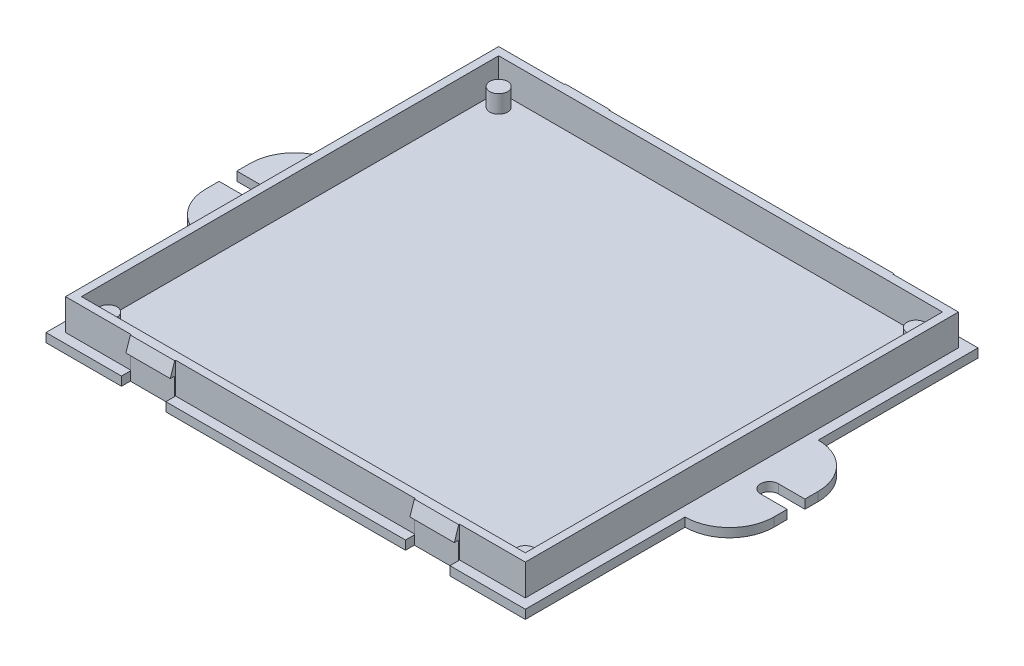
SolidWorks part; units mm, degrees
ref_plane "Front Plane" through (0, 0, 0) normal (0, 0, 1) x (1, 0, 0)
ref_plane "Top Plane" through (0, 0, 0) normal (0, 1, 0) x (1, 0, 0)
ref_plane "Right Plane" through (0, 0, 0) normal (1, 0, 0) x (0, 0, -1)
sketch "Sketch1" plane through (0, 0, 0) normal (0, 1, 0) x (1, 0, 0)
  line L1 (-54, 51) -> (54, 51)
  line L2 (-54, 51) -> (-54, -51)
  line L3 (-54, -51) -> (54, -51)
  line L4 (54, 51) -> (54, -51)
  line L5 (-54, 51) -> (54, -51) construction
  line L6 (-54, -51) -> (54, 51) construction
  point P0 (0, 0)
  dimension "D1" = 102
  dimension "D2" = 108
extrude "Boss-Extrude1" add sketch "Sketch1" along normal blind 2
sketch "Sketch2" plane through (0, 2, 0) normal (0, 1, 0) x (1, 0, 0)
  line L1 (-52, 49) -> (52, 49)
  line L2 (-52, 49) -> (-52, -49)
  line L3 (-52, -49) -> (52, -49)
  line L4 (52, 49) -> (52, -49)
  line L5 (-52, 49) -> (52, -49) construction
  line L6 (-52, -49) -> (52, 49) construction
  point P0 (0, 0)
  dimension "D1" = 98
  dimension "D2" = 104
extrude "Boss-Extrude2" add sketch "Sketch2" along normal blind 7
sketch "Sketch3" plane through (0, 9, 0) normal (0, 1, 0) x (1, 0, 0)
  line L8 (50, -47) -> (50, 47)
  line L9 (50, 47) -> (-50, 47)
  line L10 (-50, 47) -> (-50, -47)
  line L11 (-50, -47) -> (50, -47)
  line L12 (50, -47) -> (50, 47)
  line L13 (50, 47) -> (-50, 47)
  line L14 (-50, 47) -> (-50, -47)
  line L15 (-50, -47) -> (50, -47)
  dimension "D1" = 2
extrude "Cut-Extrude1" cut sketch "Sketch3" against normal blind 7
sketch "Sketch4" plane through (0, 0, 49) normal (0, 0, 1) x (1, 0, 0)
  line L0 (-52, 9) -> (-37, 9)
  line L1 (-52, 9) -> (52, 9) construction
  line L2 (52, 9) -> (32.2553, 9)
  line L4 (-37, 9) -> (-27, 9)
  line L5 (-37, 9) -> (-37, 6)
  line L6 (-37, 6) -> (-27, 6)
  line L7 (-27, 9) -> (-27, 6)
  dimension "D1" = 15
  dimension "D2" = 10
  dimension "D3" = 3
extrude "Boss-Extrude6" add sketch "Sketch4" along normal blind 1 contours L5 L4 L7 L6
sketch "Sketch5" plane through (-27, 0, 0) normal (1, 0, 0) x (0, 0, -1)
  line L0 (-50, 6) -> (-49, 9)
  line L1 (-49, 9) -> (-50, 9)
  line L2 (-50, 9) -> (-50, 5.9638)
  line M2 (-49, 9) -> (-50, 9)
  line M3 (-50, 9) -> (-50, 6)
extrude "Cut-Extrude2" cut sketch "Sketch5" against normal blind 10 contours L0 M3 M2 region at (-27, 8, 49.6667)
sketch "Sketch6" plane through (0, 0, 49) normal (0, 0, 1) x (1, 0, 0)
  line L0 (52, 9) -> (37, 9)
  line L1 (-27, 9) -> (52, 9) construction
  line L3 (37, 9) -> (27, 9)
  line L4 (37, 9) -> (37, 6)
  line L5 (37, 6) -> (27, 6)
  line L6 (27, 9) -> (27, 6)
  dimension "D1" = 15
  dimension "D2" = 10
  dimension "D3" = 3
extrude "Boss-Extrude7" add sketch "Sketch6" along normal blind 1 contours L4 L3 L6 L5
sketch "Sketch7" plane through (37, 0, 0) normal (1, 0, 0) x (0, 0, -1)
  line L0 (-50, 6) -> (-49, 9)
  line L1 (-49, 9) -> (-50, 9)
  line L2 (-50, 9) -> (-50, 6)
extrude "Cut-Extrude3" cut sketch "Sketch7" against normal blind 10
sketch "Sketch9" plane through (0, 0, -49) normal (0, 0, -1) x (-1, 0, 0)
  line L0 (-52, 9) -> (-37, 9)
  line L1 (-52, 9) -> (52, 9) construction
  line L3 (-37, 9) -> (-27, 9)
  line L4 (-37, 9) -> (-37, 6)
  line L5 (-37, 6) -> (-27, 6)
  line L6 (-27, 9) -> (-27, 6)
  dimension "D1" = 15
  dimension "D2" = 10
  dimension "D3" = 3
extrude "Boss-Extrude9" add sketch "Sketch9" along normal blind 1 contours L4 L3 L6 L5
sketch "Sketch10" plane through (27, 0, 0) normal (-1, 0, 0) x (0, 0, 1)
  line L0 (-49, 9) -> (-50, 6)
  line L1 (-50, 6) -> (-50, 9)
  line L2 (-50, 9) -> (-49, 9)
extrude "Cut-Extrude4" cut sketch "Sketch10" against normal blind 10
sketch "Sketch11" plane through (0, 0, -49) normal (0, 0, -1) x (-1, 0, 0)
  line L0 (52, 9) -> (37, 9)
  line L1 (-27, 9) -> (52, 9) construction
  line L3 (37, 9) -> (27, 9)
  line L4 (37, 9) -> (37, 6)
  line L5 (37, 6) -> (27, 6)
  line L6 (27, 9) -> (27, 6)
  dimension "D1" = 15
  dimension "D2" = 10
  dimension "D3" = 3
extrude "Boss-Extrude10" add sketch "Sketch11" along normal blind 1 contours L4 L3 L6 L5
sketch "Sketch12" plane through (-37, 0, 0) normal (-1, 0, 0) x (0, 0, 1)
  line L0 (-49, 9) -> (-50, 6)
  line L1 (-50, 6) -> (-50, 9)
  line L2 (-50, 9) -> (-49, 9)
extrude "Cut-Extrude5" cut sketch "Sketch12" against normal blind 10 contours L2 L0 L1
sketch "Sketch20" plane through (0, 0, 51) normal (0, 0, 1) x (1, 0, 0)
  line L0 (54, 2) -> (37, 2)
  line L1 (-54, 2) -> (54, 2) construction
  line L2 (-54, 0) -> (54, 0) construction
  line L3 (37, 2) -> (27, 2)
  line L4 (37, 2) -> (37, 0)
  line L5 (37, 0) -> (27, 0)
  line L6 (27, 2) -> (27, 0)
  line M6 (-54, 0) -> (54, 0)
  line M8 (54, 2) -> (-54, 2)
  dimension "D1" = 17
  dimension "D2" = 10
extrude "Cut-Extrude7" cut sketch "Sketch20" against normal blind 2 contours L6 L4 M8 M6 region at (32, 1, 51)
sketch "Sketch21" plane through (0, 2, 0) normal (0, 1, 0) x (1, 0, 0)
  line L0 (-52, -49) -> (-37, -49)
  line L1 (-52, -49) -> (27, -49) construction
  line L2 (-54, -51) -> (27, -51) construction
  line L3 (-37, -49) -> (-27, -49)
  line L4 (-37, -49) -> (-37, -51)
  line L5 (-37, -51) -> (-27, -51)
  line L6 (-27, -49) -> (-27, -51)
  dimension "D1" = 15
  dimension "D2" = 10
extrude "Cut-Extrude8" cut sketch "Sketch21" against normal blind 2 contours L4 L3 L6 L5
sketch "Sketch22" plane through (0, 2, 0) normal (0, 1, 0) x (1, 0, 0)
  line L0 (52, 49) -> (37, 49)
  line L1 (52, 49) -> (-52, 49) construction
  line L2 (54, 51) -> (-54, 51) construction
  line L3 (37, 49) -> (27, 49)
  line L4 (37, 49) -> (37, 51)
  line L5 (37, 51) -> (27, 51)
  line L6 (27, 49) -> (27, 51)
  line M6 (-52, 49) -> (52, 49)
  line M12 (54, 51) -> (-54, 51)
  dimension "D1" = 15
  dimension "D2" = 10
extrude "Cut-Extrude9" cut sketch "Sketch22" against normal blind 2 contours L6 L4 M6 M12 region at (32, 2, -50)
sketch "Sketch23" plane through (0, 2, 0) normal (0, 1, 0) x (1, 0, 0)
  line L0 (-52, 49) -> (-37, 49)
  line L1 (27, 49) -> (-52, 49) construction
  line L2 (27, 51) -> (-54, 51) construction
  line L3 (-37, 49) -> (-27, 49)
  line L4 (-37, 49) -> (-37, 51)
  line L5 (-37, 51) -> (-27, 51)
  line L6 (-27, 49) -> (-27, 51)
  dimension "D1" = 15
  dimension "D2" = 10
extrude "Cut-Extrude11" cut sketch "Sketch23" against normal blind 2 contours L4 L3 L6 L5
sketch "Sketch24" plane through (0, 2, 0) normal (0, 1, 0) x (1, 0, 0)
  line L1 (50, 47) -> (47, 47)
  line L2 (50, 47) -> (50, 44)
  line L3 (50, 44) -> (47, 44)
  line L4 (47, 47) -> (47, 44)
  circle A0 centre (47, 44) radius 2
  dimension "D1" = 3
  dimension "D2" = 3
extrude "Boss-Extrude11" add sketch "Sketch24" along normal blind 4 contours A0
sketch "Sketch25" plane through (0, 2, 0) normal (0, 1, 0) x (1, 0, 0)
  line L1 (-50, 47) -> (-47, 47)
  line L2 (-50, 47) -> (-50, 44)
  line L3 (-50, 44) -> (-47, 44)
  line L4 (-47, 47) -> (-47, 44)
  circle A0 centre (-47, 44) radius 2
  dimension "D1" = 3
  dimension "D2" = 3
extrude "Boss-Extrude12" add sketch "Sketch25" along normal blind 4 contours L3 A0 L4 | L4 A0 L3 region at (-46.7171, 2, -43.7171) region at (-47.8488, 2, -44.8488)
sketch "Sketch26" plane through (0, 2, 0) normal (0, 1, 0) x (1, 0, 0)
  line L1 (-50, -47) -> (-47, -47)
  line L2 (-50, -47) -> (-50, -44)
  line L3 (-50, -44) -> (-47, -44)
  line L4 (-47, -47) -> (-47, -44)
  circle A0 centre (-47, -44) radius 2
  dimension "D1" = 3
  dimension "D2" = 3
extrude "Boss-Extrude13" add sketch "Sketch26" along normal blind 4 contours L3 A0 L4 | L4 A0 L3 region at (-47.8488, 2, 44.8488) region at (-46.7171, 2, 43.7171)
sketch "Sketch27" plane through (0, 2, 0) normal (0, 1, 0) x (1, 0, 0)
  line L1 (50, -47) -> (47, -47)
  line L2 (50, -47) -> (50, -44)
  line L3 (50, -44) -> (47, -44)
  line L4 (47, -47) -> (47, -44)
  circle A0 centre (47, -44) radius 2
  dimension "D1" = 3
  dimension "D2" = 3
extrude "Boss-Extrude14" add sketch "Sketch27" along normal blind 4 contours L4 A0 L3 | L3 A0 L4 region at (46.7171, 2, 43.7171) region at (47.8488, 2, 44.8488)
sketch "Sketch28" plane through (-54, 0, 0) normal (-1, 0, 0) x (0, 0, 1)
  line L0 (-51, 1) -> (51, 1)
  line L1 (-51, 2) -> (-51, 0) construction
  line L2 (51, 2) -> (51, 0) construction
  line L3 (-51, 0) -> (51, 0) construction
  line L4 (-15, 2) -> (15, 2)
  line L5 (-15, 2) -> (-15, 0)
  line L6 (-15, 0) -> (15, 0)
  line L7 (15, 2) -> (15, 0)
  line L8 (-15, 2) -> (15, 0) construction
  line L9 (-15, 0) -> (15, 2) construction
  point P7 (0, 1)
  dimension "D1" = 30
extrude "Boss-Extrude15" add sketch "Sketch28" along normal blind 10 contours L6 L7 L4 L5
sketch "Sketch29" plane through (0, 2, 0) normal (0, 1, 0) x (1, 0, 0)
  line L0 (-64, 2) -> (-64, -2)
  line L1 (-64, 15) -> (-64, -15) construction
  line L3 (-64, 2) -> (-58, 2)
  line L4 (-64, 2) -> (-64, -2)
  line L5 (-64, -2) -> (-58, -2)
  line L6 (-58, 2) -> (-58, -2)
  circle A0 centre (-58, 0) radius 2
  point P5 (-64, 0)
  dimension "D1" = 4
  dimension "D2" = 6
extrude "Cut-Extrude12" cut sketch "Sketch29" against normal blind 2 contours L6 A0 | L4 L3 L6 L5 region at (-57.1512, 2, 0)
fillet "Fillet1" radius 10 2 edges at (-64, 1, 15) (-64, 1, -15)
sketch "Sketch30" plane through (54, 0, 0) normal (1, 0, 0) x (0, 0, -1)
  line L0 (-51, 1) -> (51, 1)
  line L1 (-51, 2) -> (-51, 0) construction
  line L2 (51, 2) -> (51, 0) construction
  line L3 (-51, 0) -> (51, 0) construction
  line L4 (-15, 2) -> (15, 2)
  line L5 (-15, 2) -> (-15, 0)
  line L6 (-15, 0) -> (15, 0)
  line L7 (15, 2) -> (15, 0)
  line L8 (-15, 2) -> (15, 0) construction
  line L9 (-15, 0) -> (15, 2) construction
  point P6 (0, 1)
  line M2 (-51, 0) -> (51, 0)
  line M4 (51, 2) -> (-51, 2)
  dimension "D1" = 30
extrude "Boss-Extrude16" add sketch "Sketch30" along normal blind 10 contours L7 L5 L0 M4 | L7 L0 L5 M2 region at (54, 1.5, 0) region at (54, 0.5, 0)
sketch "Sketch32" plane through (0, 2, 0) normal (0, 1, 0) x (1, 0, 0)
  line L0 (64, -2) -> (64, 2)
  line L1 (64, 15) -> (64, -15) construction
  line L3 (64, -2) -> (58, -2)
  line L4 (64, -2) -> (64, 2)
  line L5 (64, 2) -> (58, 2)
  line L6 (58, -2) -> (58, 2)
  circle A0 centre (58, 0) radius 2
  point P5 (64, 0)
  line M14 (64, -15) -> (64, 15)
  dimension "D1" = 4
  dimension "D2" = 6
extrude "Cut-Extrude13" cut sketch "Sketch32" against normal blind 2 contours A0 L3 L5 M14 | L6 A0 | L6 A0 region at (61.7629, 2, 0) region at (57.1512, 2, 0) region at (58.8488, 2, 0)
fillet "Fillet2" radius 10 2 edges at (64, 1, -15) (64, 1, 15)
sketch "Sketch33" plane through (0, 9, 0) normal (0, 1, 0) x (1, 0, 0)
  line L0 (52, 49) -> (37, 49) construction
  line L1 (52, -49) -> (51.8, -49)
  line L2 (52, -49) -> (52, 49)
  line L3 (52, 49) -> (51.8, 49)
  line L4 (51.8, -49) -> (51.8, 49)
  dimension "D1" = 0.2
extrude "Cut-Extrude14" cut sketch "Sketch33" against normal blind 7
sketch "Sketch34" plane through (0, 9, 0) normal (0, 1, 0) x (1, 0, 0)
  line L1 (51.8, 49) -> (37, 49)
  line L2 (51.8, 49) -> (51.8, 48.8)
  line L3 (51.8, 48.8) -> (37, 48.8)
  line L4 (37, 49) -> (37, 48.8)
  dimension "D1" = 0.2
extrude "Cut-Extrude15" cut sketch "Sketch34" against normal blind 7
sketch "Sketch35" plane through (0, 9, 0) normal (0, 1, 0) x (1, 0, 0)
  line L1 (27, 49) -> (-27, 49)
  line L2 (27, 49) -> (27, 48.8)
  line L3 (27, 48.8) -> (-27, 48.8)
  line L4 (-27, 49) -> (-27, 48.8)
  dimension "D1" = 0.2
extrude "Cut-Extrude16" cut sketch "Sketch35" against normal blind 7
sketch "Sketch36" plane through (0, 9, 0) normal (0, 1, 0) x (1, 0, 0)
  line L0 (-52, 49) -> (-52, -49) construction
  line L1 (-37, 49) -> (-52, 49)
  line L2 (-37, 49) -> (-37, 48.8)
  line L3 (-37, 48.8) -> (-52, 48.8)
  line L4 (-52, 49) -> (-52, 48.8)
  dimension "D1" = 0.2
extrude "Cut-Extrude17" cut sketch "Sketch36" against normal blind 7
sketch "Sketch37" plane through (0, 9, 0) normal (0, 1, 0) x (1, 0, 0)
  line L0 (-52, -49) -> (-37, -49) construction
  line L1 (-52, 48.8) -> (-51.8, 48.8)
  line L2 (-52, 48.8) -> (-52, -49)
  line L3 (-52, -49) -> (-51.8, -49)
  line L4 (-51.8, 48.8) -> (-51.8, -49)
  dimension "D1" = 0.2
extrude "Cut-Extrude18" cut sketch "Sketch37" against normal blind 7
sketch "Sketch39" plane through (0, 9, 0) normal (0, 1, 0) x (1, 0, 0)
  line L1 (-51.8, -49) -> (-37, -49)
  line L2 (-51.8, -49) -> (-51.8, -48.8)
  line L3 (-51.8, -48.8) -> (-37, -48.8)
  line L4 (-37, -49) -> (-37, -48.8)
  dimension "D1" = 0.2
extrude "Cut-Extrude19" cut sketch "Sketch39" against normal blind 7
sketch "Sketch41" plane through (0, 9, 0) normal (0, 1, 0) x (1, 0, 0)
  line L1 (-27, -49) -> (26.9963, -49)
  line L2 (-27, -49) -> (-27, -48.8)
  line L3 (-27, -48.8) -> (26.9963, -48.8)
  line L4 (26.9963, -49) -> (26.9963, -48.8)
  dimension "D1" = 0.2
extrude "Cut-Extrude20" cut sketch "Sketch41" against normal blind 7
sketch "Sketch42" plane through (0, 9, 0) normal (0, 1, 0) x (1, 0, 0)
  line L0 (51.8, 48.8) -> (51.8, -49) construction
  line L1 (37, -49) -> (51.8, -49)
  line L2 (37, -49) -> (37, -48.8)
  line L3 (37, -48.8) -> (51.8, -48.8)
  line L4 (51.8, -49) -> (51.8, -48.8)
  dimension "D1" = 0.2
extrude "Cut-Extrude21" cut sketch "Sketch42" against normal blind 7
